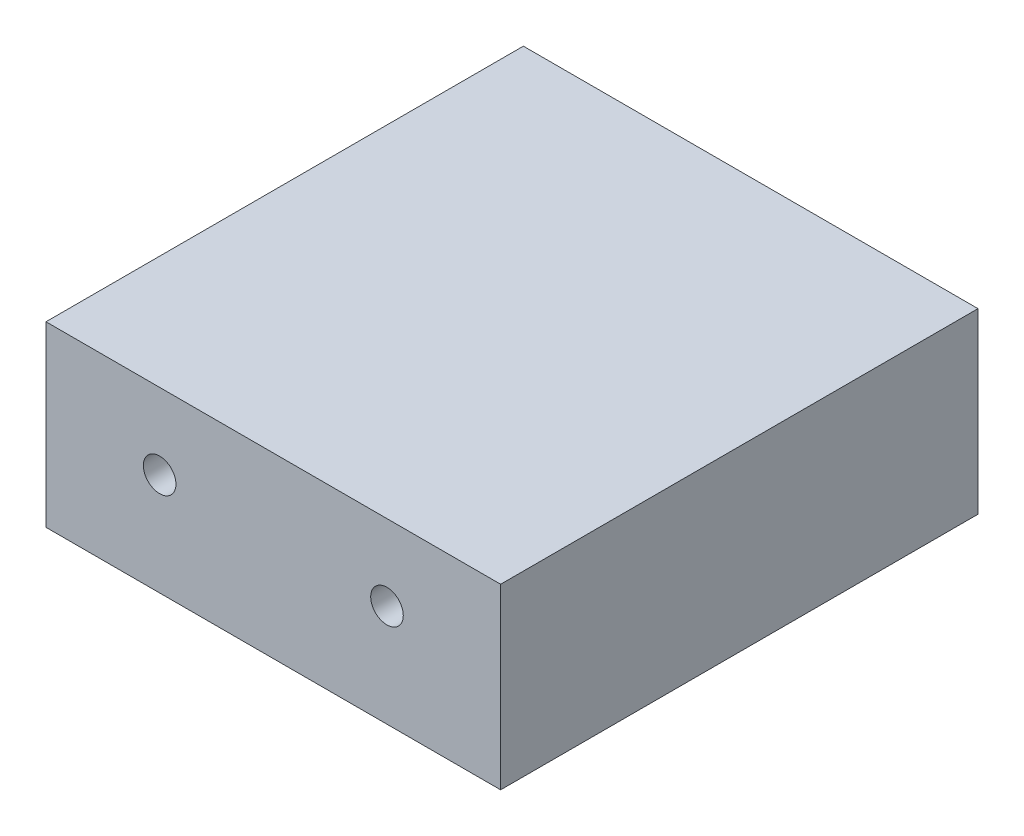
SolidWorks part; units mm, degrees
ref_plane "Front Plane" through (0, 0, 0) normal (0, 0, 1) x (1, 0, 0)
ref_plane "Top Plane" through (0, 0, 0) normal (0, 1, 0) x (1, 0, 0)
ref_plane "Right Plane" through (0, 0, 0) normal (1, 0, 0) x (0, 0, -1)
sketch "SK_Top" plane through (0, 0, 0) normal (0, 1, 0) x (1, 0, 0)
  line L1 (-30, 25) -> (30, 25)
  line L2 (-30, 25) -> (-30, -38)
  line L3 (-30, -38) -> (30, -38)
  line L4 (30, 25) -> (30, -38)
  dimension "D1" = 63
  dimension "D2" = 60
  dimension "D3" = 25
  dimension "D4" = 30
extrude "EX_Top" add sketch "SK_Top" along normal blind 23.5
ref_plane "PL_Xp38" through (0, 0, 38) normal (0, 0, 1) x (1, 0, 0)
sketch "SK_RailBolts" plane through (0, 0, 38) normal (0, 0, 1) x (1, 0, 0)
  circle A0 centre (15, 13.5) radius 2.15
  circle A1 centre (-15, 13.5) radius 2.15
  dimension "D3" = 4.3
  dimension "D6" = 4.3
  dimension "D1" = 15
  dimension "D2" = 13.5
  dimension "D4" = 15
  dimension "D5" = 13.5
extrude "CUT_RailBolts" cut sketch "SK_RailBolts" against normal blind 8
sketch "SK_Inserts_M4" plane through (0, 0, 0) normal (0, 1, 0) x (1, 0, 0)
  circle A0 centre (15, -15) radius 2.8
  circle A1 centre (-15, -15) radius 2.8
  circle A2 centre (15, 15) radius 2.8
  circle A3 centre (-15, 15) radius 2.8
  dimension "D3" = 5.6
  dimension "D6" = 5.6
  dimension "D9" = 5.6
  dimension "D12" = 5.6
  dimension "D1" = 15
  dimension "D2" = 15
  dimension "D4" = 15
  dimension "D5" = 15
  dimension "D7" = 15
  dimension "D8" = 15
  dimension "D10" = 15
  dimension "D11" = 15
extrude "CUT_Inserts_M4" cut sketch "SK_Inserts_M4" along normal blind 8.1
ref_axis "AX_X" through (0, 0, -28.15) along (0, 0, 1)
ref_axis "AX_Y" through (33, 0, 0) along (-1, 0, 0)
ref_axis "AX_Z" through (0, 24.675, 0) along (0, -1, 0)
